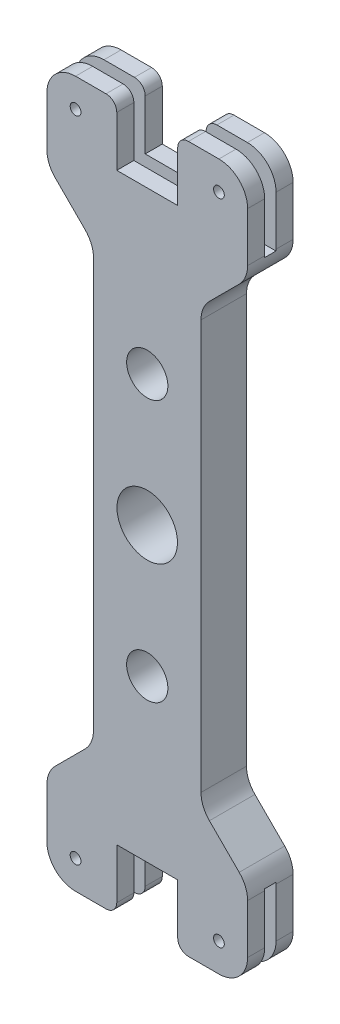
SolidWorks part; units mm, degrees
ref_plane "Front Plane" through (0, 0, 0) normal (0, 0, 1) x (1, 0, 0)
ref_plane "Top Plane" through (0, 0, 0) normal (0, 1, 0) x (1, 0, 0)
ref_plane "Right Plane" through (0, 0, 0) normal (1, 0, 0) x (0, 0, -1)
sketch "Sketch1" plane through (0, 0, 0) normal (0, 0, 1) x (1, 0, 0)
  line L1 (0, -5.2388) -> (0, 5.2388) construction
  line L2 (5.2388, 0) -> (-5.2388, 0) construction
  line L3 (-28, 73.3978) -> (-28, 90.475)
  line L4 (-20, 98.475) -> (-11.5, 98.475)
  line L5 (28, 90.475) -> (28, 73.3978)
  line L6 (28, 73.3978) -> (15, 60.3978)
  line L7 (15, 60.3978) -> (15, -60.3978)
  line L13 (-15, -60.3978) -> (-15, 60.3978)
  line L14 (-15, 60.3978) -> (-28, 73.3978)
  line L15 (0, -1000) -> (0, 49000) construction
  line L16 (-1000, 0) -> (49000, 0) construction
  line L17 (-8.5, 95.475) -> (-8.5, 81.475)
  line L18 (-8.5, 81.475) -> (8.5, 81.475)
  line L19 (8.5, 81.475) -> (8.5, 95.475)
  line L20 (11.5, 98.475) -> (20, 98.475)
  line L21 (-20, 98.475) -> (-20, 90.475) construction
  line L22 (-20, 90.475) -> (-28, 90.475) construction
  line L23 (-8.5, 81.475) -> (-22.2886, 67.6864) construction
  line L24 (-8.5, 81.475) -> (-28, 81.475) construction
  line L25 (28, -73.3978) -> (15, -60.3978)
  line L26 (28, -90.475) -> (28, -73.3978)
  line L27 (11.5, -98.475) -> (20, -98.475)
  line L28 (8.5, -81.475) -> (8.5, -95.475)
  line L29 (-8.5, -81.475) -> (8.5, -81.475)
  line L30 (-8.5, -95.475) -> (-8.5, -81.475)
  line L31 (-20, -98.475) -> (-11.5, -98.475)
  line L32 (-28, -73.3978) -> (-28, -90.475)
  line L33 (-15, -60.3978) -> (-28, -73.3978)
  circle A0 centre (0, 0) radius 8.4375
  circle A1 centre (-20, 90.475) radius 1.5
  circle A3 centre (20, 90.475) radius 1.5
  circle A4 centre (20, -90.475) radius 1.5
  circle A5 centre (-20, -90.475) radius 1.5
  arc A6 (-28, 90.475) -> (-20, 98.475) centre (-20, 90.475) cw
  arc A7 (20, 98.475) -> (28, 90.475) centre (20, 90.475) cw
  arc A8 (20, -98.475) -> (28, -90.475) centre (20, -90.475) ccw
  arc A9 (-28, -90.475) -> (-20, -98.475) centre (-20, -90.475) ccw
  arc A10 (-8.5, -95.475) -> (-11.5, -98.475) centre (-11.5, -95.475) cw
  arc A11 (11.5, -98.475) -> (8.5, -95.475) centre (11.5, -95.475) cw
  arc A12 (8.5, 95.475) -> (11.5, 98.475) centre (11.5, 95.475) cw
  arc A13 (-8.5, 95.475) -> (-11.5, 98.475) centre (-11.5, 95.475) ccw
  point P22 (0, 81.475)
  point P39 (15, 0)
  point P51 (-15, 0)
  point P53 (-8.5, -98.475)
  point P56 (8.5, -98.475)
  point P59 (8.5, 98.475)
  point P62 (-8.5, 98.475)
  dimension "D1" = 16.875
  dimension "D9" = 3
  dimension "D3" = 30
  dimension "D4" = 17
  dimension "D5" = 40
  dimension "D6" = 8
  dimension "D7" = 180.95
  dimension "D8" = 45
  dimension "D10" = 17
extrude "Boss-Extrude1" add sketch "Sketch1" along normal mid plane 12.7
fillet "Fillet1" radius 8 8 edges at (-28, 73.3978, 0) (-15, 60.3978, 0) (-28, -73.3978, 0) (-15, -60.3978, 0) (15, -60.3978, 0) (28, -73.3978, 0) (28, 73.3978, 0) (15, 60.3978, 0)
sketch "Sketch3" plane through (0, 98.475, 0) normal (0, 1, 0) x (1, 0, 0)
  line L0 (-28, -6.35) -> (-28, 6.35) construction
  line L1 (28, 1.5875) -> (-28, 1.5875)
  line L2 (28, 1.5875) -> (28, -1.5875)
  line L3 (28, -1.5875) -> (-28, -1.5875)
  line L4 (-28, 1.5875) -> (-28, -1.5875)
  line L5 (28, 1.5875) -> (-28, -1.5875) construction
  line L6 (28, -1.5875) -> (-28, 1.5875) construction
  point P0 (0, 0)
  dimension "D1" = 3.175
extrude "Cut-Extrude1" cut sketch "Sketch3" against normal blind 22.22
mirror "Mirror1" about plane through (0, 0, 0) normal (0, 1, 0) of "Cut-Extrude1"
sketch "Sketch4" plane through (0, 0, 6.35) normal (0, 0, 1) x (1, 0, 0)
  line L0 (0, 36.5125) -> (0, -36.5125) construction
  point P0 (0, 36.5125)
  point P2 (0, -36.5125)
  point P4 (0, 0)
  point P19 (0, 0)
  dimension "D2" = 73.025
hole_wizard "7/16 Clearance Hole4" positions "Sketch4" profile "Sketch5" hole size "7/16" standard "ANSI Inch" end condition through all
sketch "Sketch5" plane through (0, 36.5125, 6.35) normal (1, 0, 0) x (0, -1, 0)
  line L0 (0, 0) -> (0, 12.7)
  line L1 (0, 12.7) -> (5.7544, 12.7)
  line L2 (5.7544, 12.7) -> (5.7544, 0)
  line L5 (5.7544, 0) -> (0, 0)
  line L11 (0, -6.35) -> (0, 107.95) construction
  dimension "Thru Hole Dia." = 11.5087
  dimension "Thru Hole Depth" = 12.7
equation "\"D1@Fillet1\"=\"D6@Sketch1\""
equation "\"Shaft Size\"= 5in / 8"
equation "\"Bearing Screw Spacing\" = 2.875in"
equation "\"D1@Sketch1\"= \"Shaft Size\" + 1mm"
equation "\"D2@Sketch4\"= \"Bearing Screw Spacing\""
equation "\"Plate Thickness\"= 1in / 2"
equation "\"D1@Boss-Extrude1\"=\"Plate Thickness\""
